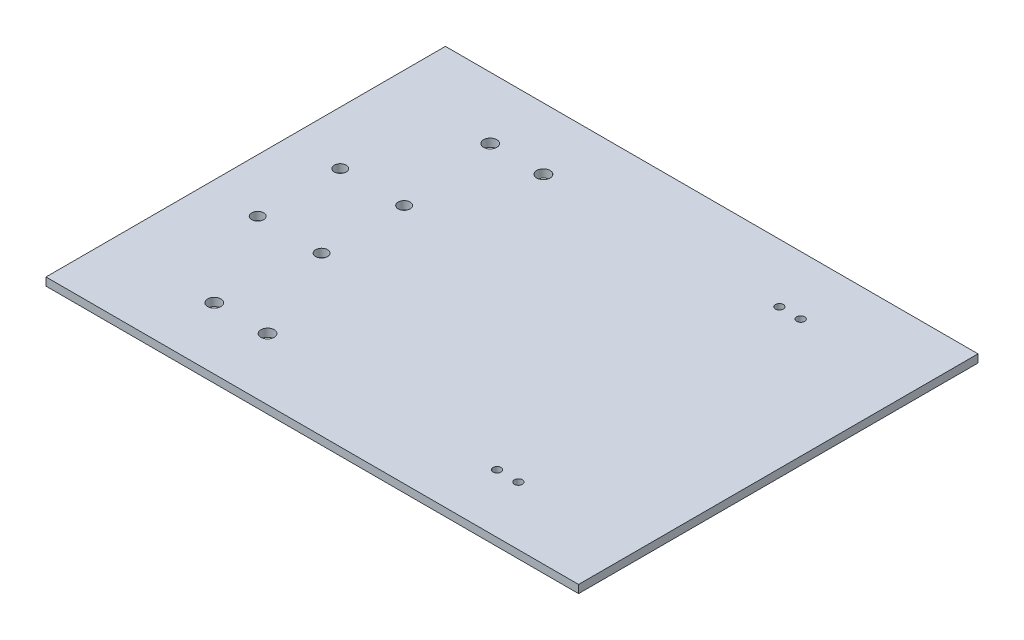
SolidWorks part; units mm, degrees
ref_plane "Front Plane" through (0, 0, 0) normal (0, 0, 1) x (1, 0, 0)
ref_plane "Top Plane" through (0, 0, 0) normal (0, 1, 0) x (1, 0, 0)
ref_plane "Right Plane" through (0, 0, 0) normal (1, 0, 0) x (0, 0, -1)
sketch "Sketch2" plane through (0, 0, 0) normal (0, 1, 0) x (1, 0, 0)
  line L1 (0, 0) -> (200, 0)
  line L2 (0, 0) -> (0, 150)
  line L3 (0, 150) -> (200, 150)
  line L4 (200, 0) -> (200, 150)
  dimension "D1" = 200
  dimension "D2" = 150
extrude "Boss-Extrude1" add sketch "Sketch2" along normal blind 3
sketch "Sketch3" plane through (0, 3, 0) normal (0, 1, 0) x (1, 0, 0)
  line L0 (0, 150) -> (0, 0) construction
  line L1 (200, 0) -> (200, 150) construction
  line L2 (100, 150) -> (100, 0) construction
  line L3 (200, 150) -> (0, 150) construction
  line L4 (0, 0) -> (200, 0) construction
  line L5 (0, 75) -> (200, 75) construction
  line L6 (0, 150) -> (0, 0) construction
  line L7 (200, 0) -> (200, 150) construction
  line L8 (0, 0) -> (200, 0) construction
  line L9 (200, 150) -> (0, 150) construction
  circle A9 centre (155.4, 128) radius 1.5
  circle A10 centre (147.4, 128) radius 1.5
  circle A11 centre (147.4, 22) radius 1.5
  circle A12 centre (155.4, 22) radius 1.5
  circle A13 centre (20, 90.5) radius 2.25
  circle A14 centre (44, 90.5) radius 2.25
  circle A15 centre (44, 59.5) radius 2.25
  circle A16 centre (20, 59.5) radius 2.25
  circle A17 centre (40, 23.2) radius 2.5
  circle A18 centre (60, 23.2) radius 2.5
  circle A19 centre (60, 126.8) radius 2.5
  circle A20 centre (40, 126.8) radius 2.5
  dimension "D1" = 3
  dimension "D2" = 44.6
  dimension "D3" = 22
  dimension "D4" = 3
  dimension "D5" = 22
  dimension "D6" = 8
  dimension "D7" = 4.5
  dimension "D8" = 4.5
  dimension "D9" = 24
  dimension "D10" = 15.5
  dimension "D11" = 15.5
  dimension "D12" = 20
  dimension "D13" = 20
  dimension "D14" = 23.2
  dimension "D15" = 23.2
  dimension "D16" = 5
  dimension "D17" = 5
  dimension "D18" = 40
extrude "Cut-Extrude1" cut sketch "Sketch3" against normal blind 10
